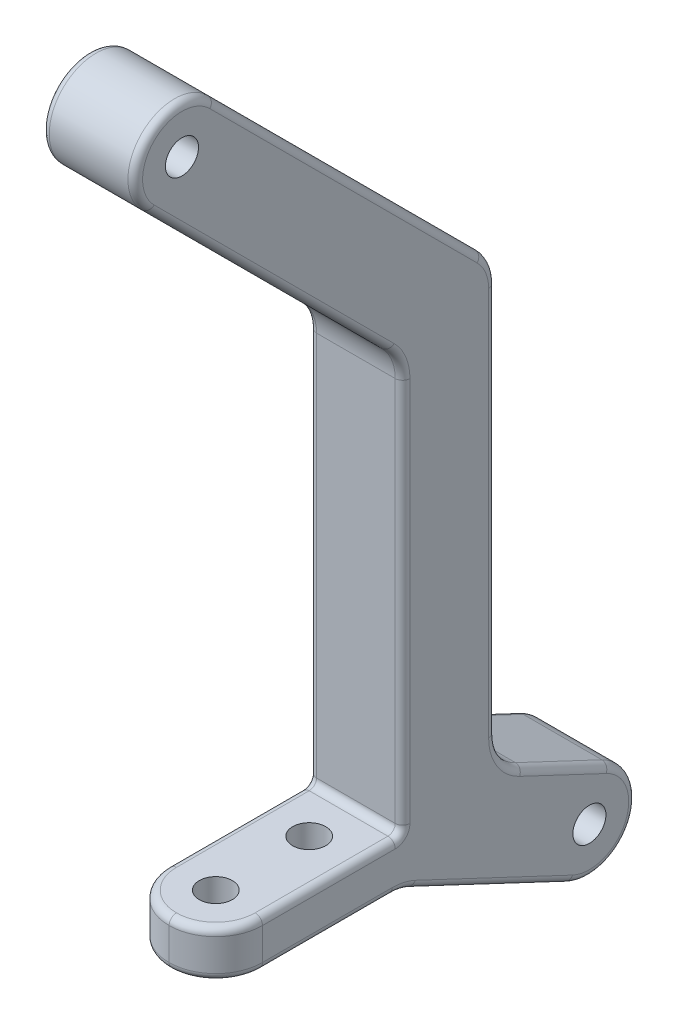
SolidWorks part; units mm, degrees
ref_plane "Front Plane" through (0, 0, 0) normal (0, 0, 1) x (1, 0, 0)
ref_plane "Top Plane" through (0, 0, 0) normal (0, 1, 0) x (1, 0, 0)
ref_plane "Right Plane" through (0, 0, 0) normal (1, 0, 0) x (0, 0, -1)
sketch "Sketch1" plane through (0, 0, 0) normal (1, 0, 0) x (0, 0, -1)
  line L0 (-25.4, 11.3) -> (-50.8, 11.3)
  line L1 (-50.8, 11.3) -> (-50.8, 4.95)
  line L2 (-50.8, 4.95) -> (-25.4, 4.95)
  line L3 (-12.7, 13.0047) -> (2.7069, 5.7441)
  line L4 (-25.4, 4.95) -> (-2.7069, -5.7441)
  line L6 (-25.4, 11.3) -> (-25.4, 67.3197)
  line L7 (-25.4, 67.3197) -> (-59.8901, 101.8099)
  line L8 (-50.9099, 110.7901) -> (-12.7, 72.5803)
  line L9 (-12.7, 72.5803) -> (-12.7, 13.0047)
  circle A0 centre (0, 0) radius 2.25
  circle A2 centre (-55.4, 106.3) radius 2.25
  circle A3 centre (-55.4, 106.3) radius 6.35
  circle A4 centre (0, 0) radius 6.35
  dimension "D1" = 4.5
  dimension "D3" = 6.35
  dimension "D6" = 12.7
  dimension "D8" = 4.5
  dimension "D10" = 12.7
  dimension "D7" = 12.7
  dimension "D2" = 11.3
  dimension "D4" = 25.4
  dimension "D5" = 25.4
  dimension "D9" = 95
  dimension "D11" = 30
  dimension "D12" = 45
extrude "Boss-Extrude1" add sketch "Sketch1" along normal blind 12.7 contours A3 L7 L6 L0 L1 L2 L9 L8 A0 | A3 A2 | A4 A0 region at (0, 39.3099, 24.0772) region at (0, 110.6631, 59.7631) region at (0, 2.6304, 5.5817)
fillet "Fillet1" radius 6.35 4 edges at (6.35, 72.5803, 12.7) (6.35, 67.3197, 25.4) (6.35, 4.95, 25.4) (6.35, 13.0047, 12.7)
fillet "Fillet3" radius 6.35 2 edges at (0, 8.125, 50.8) (12.7, 8.125, 50.8)
fillet "Fillet4" radius 1 33 edges at (10.8401, 11.3, 48.9401) (1.8599, 11.3, 48.9401) (12.7, 11.3, 34.925) (0, 11.3, 34.925) (12.7, 37.9947, 25.4) (0, 37.9947, 25.4) (12.7, 67.1195, 25.8834) (0, 67.1195, 25.8834) (12.7, 85.4947, 43.575) (0, 85.4947, 43.575) (12.7, 110.7901, 59.8901) (0, 110.7901, 59.8901) (12.7, 92.6151, 32.7349) (0, 92.6151, 32.7349) (12.7, 72.38, 13.1834) (0, 72.38, 13.1834) (12.7, 43.491, 12.7) (0, 43.491, 12.7) (12.7, 4.95, 35.6356) (10.8401, 4.95, 48.9401) (1.8599, 4.95, 48.9401) (0, 4.95, 35.6356) (6.35, 11.3, 25.4) (12.7, 13.631, 11.7124) (12.7, 8.516, 3.175) (12.7, -2.7069, -5.7441) (12.7, -0.7, 13.4106) (12.7, 4.7967, 25.4343) (0, 13.631, 11.7124) (0, 8.516, 3.175) (0, -2.7069, -5.7441) (0, -0.7, 13.4106) (0, 4.7967, 25.4343)
sketch "Sketch2" plane through (0, 4.95, 0) normal (0, -1, 0) x (1, 0, 0)
  line L1 (0, 26.8213) -> (0, 44.45) construction
  circle A0 centre (6.35, 31.75) radius 2.25
  circle A1 centre (6.35, 44.45) radius 2.25
  dimension "D1" = 4.5
  dimension "D2" = 12.7
  dimension "D3" = 31.75
  dimension "D4" = 6.35
extrude "Cut-Extrude1" cut sketch "Sketch2" against normal up to next
